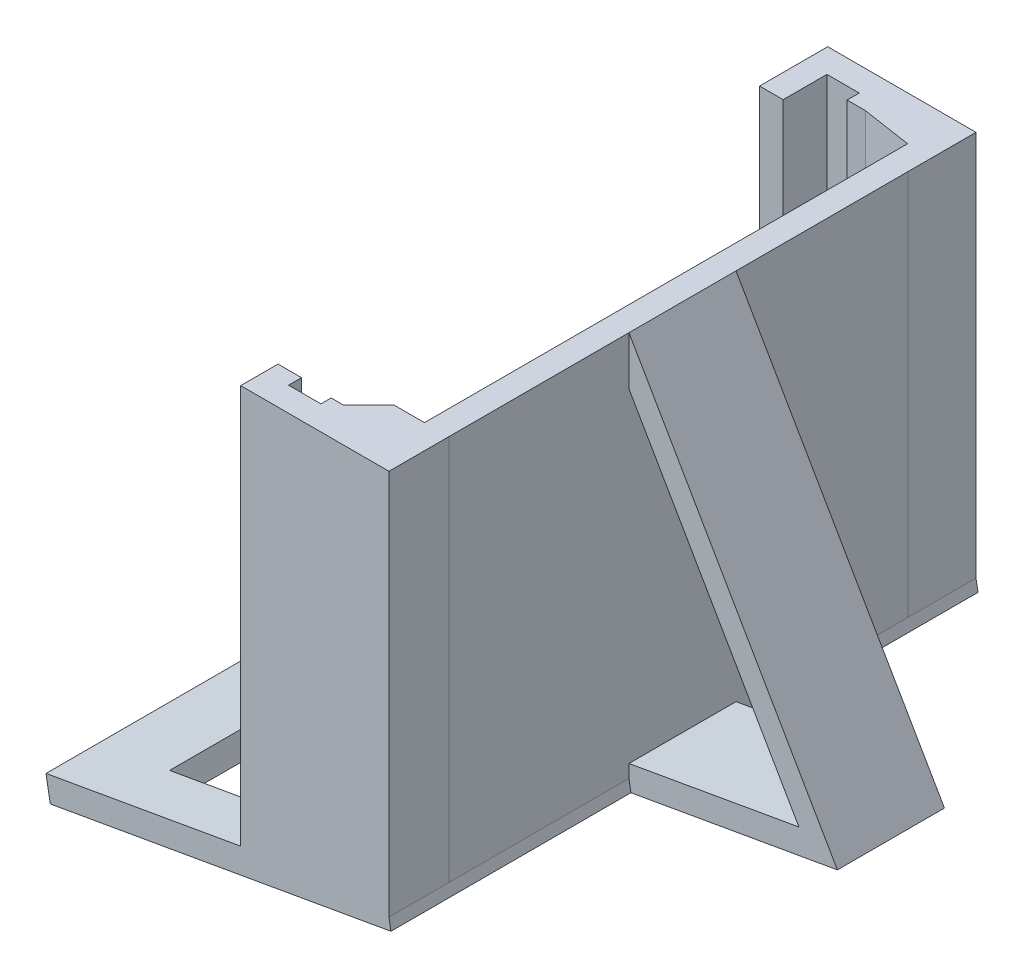
SolidWorks part; units mm, degrees
ref_plane "Front Plane" through (0, 0, 0) normal (0, 0, 1) x (1, 0, 0)
ref_plane "Top Plane" through (0, 0, 0) normal (0, 1, 0) x (1, 0, 0)
ref_plane "Right Plane" through (0, 0, 0) normal (1, 0, 0) x (0, 0, -1)
sketch "Sketch1" plane through (0, 0, 0) normal (0, 1, 0) x (1, 0, 0)
  line L1 (0, 0) -> (38.6999, 0)
  line L2 (0, 0) -> (0, 153.1937)
  line L3 (0, 153.1937) -> (38.6999, 153.1937)
  line L4 (38.6999, 0) -> (38.6999, 153.1937)
  dimension "D1" = 38.6999
  dimension "D2" = 153.1937
extrude "Boss-Extrude1" add sketch "Sketch1" along normal blind 0.0254 contours L1 L4 L3 L2 | L2 region at (19.35, 0, -76.5969)
sketch "Sketch3" plane through (0, 0.0254, 0) normal (0, 1, 0) x (1, 0, 0)
  line L0 (6.65, 146.8438) -> (6.15, 146.8438)
  line L1 (6.65, 146.8438) -> (14.5875, 146.8438)
  line L2 (14.5875, 146.8438) -> (14.5875, 143.6687)
  line L3 (14.5875, 143.6687) -> (32.05, 143.6687)
  line L4 (6.15, 146.8438) -> (6.15, 135.4137)
  line L7 (32.05, 143.6687) -> (32.35, 143.6687)
  line L8 (32.35, 143.6687) -> (32.35, 135.4137)
  line L9 (32.35, 135.4137) -> (38.7, 135.4137)
  line L10 (38.7, 135.4137) -> (38.7, 153.1937)
  line L11 (38.7, 153.1937) -> (0, 153.1937)
  line L12 (6.15, 135.4137) -> (0, 135.4137)
  line L13 (0, 153.1937) -> (0, 135.4137)
  line L15 (0, 153.1937) -> (38.6999, 153.1937) construction
  line L16 (14.5875, 9.025) -> (17.7625, 9.025)
  line L17 (10.6187, 146.8438) -> (10.6187, 76.5969) construction
  line L18 (10.6187, 76.5969) -> (61.4187, 76.5969) construction
  line L19 (38.6999, 0) -> (0, 0)
  line L20 (38.6999, 15.6157) -> (38.6999, 0)
  line L25 (14.5875, 6.35) -> (14.5875, 9.025)
  line L26 (6.65, 6.35) -> (14.5875, 6.35)
  line L27 (6.65, 6.35) -> (6.15, 6.35)
  line L28 (6.15, 6.35) -> (6.15, 9.7407)
  line L29 (6.15, 9.7407) -> (0, 9.7407)
  line L30 (0, 0) -> (0, 9.7407)
  line L31 (17.7625, 9.025) -> (24.3532, 15.6157)
  line L32 (24.3532, 15.6157) -> (38.6999, 15.6157)
  line L33 (19.35, 143.6687) -> (32.35, 141.6844)
  line L34 (38.6999, 0) -> (38.6999, 153.1937) construction
  line L35 (0, 0) -> (38.6999, 0) construction
  point P19 (10.6187, 146.8438)
  dimension "D1" = 17.4625
  dimension "D2" = 7.9375
  dimension "D3" = 3.175
  dimension "D4" = 11.43
  dimension "D5" = 0.5
  dimension "D6" = 0.3
  dimension "D7" = 0
  dimension "D8" = 38.6999
  dimension "D9" = 6.15
  dimension "D10" = 6.35
  dimension "D11" = 6.35
  dimension "D12" = 6.35
  dimension "D13" = 70.2469
  dimension "D14" = 50.8
  dimension "D15" = 3.175
  dimension "D16" = 135
  dimension "D17" = 14.3467
  dimension "D18" = 90
  dimension "D19" = 90
  dimension "D20" = 90
  dimension "D21" = 4.7625
  dimension "D22" = 1.9844
  dimension "D23" = 0
  dimension "D24" = 270
  dimension "D25" = 9.7407
  dimension "D26" = 6.5907
  dimension "D27" = 90
  dimension "D28" = 2.675
extrude "Boss-Extrude2" add sketch "Sketch3" along normal blind 104.14 contours L13 L12 L4 L0 L1 L2 L3 L7 L8 L9 L10 | L30 L19 L20 L25 L26 L27 L28 L29 | L3 L33 L8 L7 region at (19.9393, 0.0254, -146.561) region at (28.0167, 0.0254, -143.0073) region at (22.3528, 0.0254, -6.3762)
sketch "Sketch6" plane through (0, 0, -135.4137) normal (0, 0, 1) x (1, 0, 0)
  line L1 (32.35, 104.1654) -> (38.7, 104.1654)
  line L2 (32.35, 104.1654) -> (32.35, 0.0254)
  line L3 (32.35, 0.0254) -> (38.7, 0.0254)
  line L4 (38.7, 104.1654) -> (38.7, 0.0254)
  dimension "D1" = 104.14
  dimension "D2" = 6.35
extrude "Boss-Extrude3" add sketch "Sketch6" along normal up to surface (119.798 mm away) up to face at (31.5266, 52.0954, -15.6157)
sketch "Sketch15" plane through (0, 0, 0) normal (0, 0, 1) x (1, 0, 0)
  line L0 (0, 0) -> (38.6999, 0) construction
  line L1 (-50.8, -8.8719) -> (-49.6803, -15.2219)
  line L2 (127, 22.479) -> (-127, -22.3081) construction
  line L3 (0, 104.1654) -> (0, 0) construction
  line L4 (-49.6803, -15.2219) -> (39.2197, 0.4535)
  line L5 (39.2197, 0.4535) -> (38.1, 6.8035)
  line L6 (38.1, 6.8035) -> (-50.8, -8.8719)
  dimension "D1" = 10
  dimension "D2" = 254
  dimension "D3" = 127
  dimension "D4" = 22.479
  dimension "D5" = 6.35
  dimension "D6" = 88.9
  dimension "D7" = 38.1
extrude "Boss-Extrude7" add sketch "Sketch15" against normal up to surface (153.1937 mm away) up to face at (19.35, 52.0827, -153.1937)
sketch "Sketch11" plane through (0, 0, -153.1937) normal (0, 0, -1) x (-1, 0, 0)
  line L0 (-38.6999, 104.1654) -> (-93.0935, 9.9529)
  line L1 (-38.6999, 104.1654) -> (-38.6999, 3.4011) construction
  line L2 (-38.6999, 104.1654) -> (0, 104.1654) construction
  line L4 (-38.6999, 91.4654) -> (-86.4387, 8.7795)
  line L5 (-86.4387, 8.7795) -> (-93.0935, 9.9529)
  line L6 (-38.6999, 91.4654) -> (-38.6999, 104.1654)
  line L7 (49.6803, -15.2219) -> (-36.6476, 0) construction
  dimension "D1" = 12.7
  dimension "D2" = 30
  dimension "D3" = 0
  dimension "D4" = 30
  dimension "D5" = 12.7
  dimension "D6" = 0
extrude "Boss-Extrude5" add sketch "Sketch11" along direction (0, 0, -1) on the side against the normal blind 27.94 from offset 62.6269 contours L6 L0 L5 L4 offset against normal yes
sketch "Sketch14" plane through (0, 0, -153.1937) normal (0, 0, -1) x (-1, 0, 0)
  line L1 (-26, 40.005) -> (-14.5875, 40.005)
  line L2 (-26, 40.005) -> (-26, 59.055)
  line L3 (-26, 59.055) -> (-14.5875, 59.055)
  line L4 (-14.5875, 40.005) -> (-14.5875, 59.055)
  line L6 (-14.5875, 104.1654) -> (-14.5875, 2.6576) construction
  line L7 (-32.35, 104.1654) -> (-32.35, 5.7897) construction
  line L8 (0, 0.0855) -> (0, 104.1654) construction
  line L9 (0, 104.1654) -> (0, 0.0855) construction
  line L10 (0, 0.0855) -> (-39.2846, 0.0855) construction
  line L11 (-39.2197, 0.4535) -> (-38.6999, 3.4011) construction
  dimension "D1" = 19.05
  dimension "D2" = 39.9195
  dimension "D3" = 0
  dimension "D4" = 6.35
  dimension "D5" = 0
extrude "Cut-Extrude1" cut sketch "Sketch14" against normal up to next
sketch "Sketch18" plane through (38.1146, 6.7206, 0) normal (0.9848, 0.1736, 0) x (0, 0, -1)
  line L0 (153.1937, -6.3638) -> (0, -6.3638) construction
  line L1 (62.6269, -6.3638) -> (90.5669, -6.3638)
  line L2 (62.6269, -6.3638) -> (62.6269, -0.0138)
  line L3 (62.6269, -0.0138) -> (90.5669, -0.0138)
  line L4 (90.5669, -6.3638) -> (90.5669, -0.0138)
  line L5 (90.5669, 83.3556) -> (90.5669, -6.3638) construction
  dimension "D1" = 27.94
  dimension "D2" = 0
  dimension "D3" = 6.35
extrude "Boss-Extrude8" add sketch "Sketch18" along normal up to next
sketch "Sketch19" plane through (-0.0146, 0.0829, 0) normal (-0.1736, 0.9848, 0) x (0.9848, 0.1736, 0)
  line L0 (-51.5688, 153.1937) -> (-51.5688, 0) construction
  line L1 (-32.5188, 134.1437) -> (-13.4688, 134.1437)
  line L2 (-32.5188, 134.1437) -> (-32.5188, 115.0937)
  line L3 (-32.5188, 115.0937) -> (-13.4688, 115.0937)
  line L4 (-13.4688, 134.1437) -> (-13.4688, 115.0937)
  line L5 (0.0148, 153.1937) -> (-51.5688, 153.1937) construction
  line L6 (-32.5188, 108.7437) -> (-32.5188, 89.6937)
  line L7 (-32.5188, 108.7437) -> (-13.4688, 108.7437)
  line L8 (-13.4688, 108.7437) -> (-13.4688, 89.6937)
  line L9 (-32.5188, 89.6937) -> (-13.4688, 89.6937)
  line L10 (-32.5188, 83.3438) -> (-32.5188, 64.2938)
  line L11 (-32.5188, 83.3438) -> (-13.4688, 83.3438)
  line L12 (-13.4688, 83.3438) -> (-13.4688, 64.2938)
  line L13 (-32.5188, 64.2938) -> (-13.4688, 64.2938)
  line L14 (-32.5188, 57.9438) -> (-32.5188, 38.8938)
  line L15 (-32.5188, 57.9438) -> (-13.4688, 57.9438)
  line L16 (-13.4688, 57.9438) -> (-13.4688, 38.8938)
  line L17 (-32.5188, 38.8938) -> (-13.4688, 38.8938)
  line L18 (-32.5188, 32.5438) -> (-32.5188, 13.4938)
  line L19 (-32.5188, 32.5438) -> (-13.4688, 32.5438)
  line L20 (-13.4688, 32.5438) -> (-13.4688, 13.4938)
  line L21 (-32.5188, 13.4938) -> (-13.4688, 13.4938)
  dimension "D1" = 19.05
  dimension "D2" = 19.05
  dimension "D3" = 19.05
  dimension "D4" = 19.05
  dimension "D6" = 6.35
  dimension "D5" = 5
extrude "Cut-Extrude2" cut sketch "Sketch19" against normal through all
sketch "Sketch20" plane through (1.1051, -6.2671, 0) normal (0.1736, -0.9848, 0) x (0.9848, 0.1736, 0)
  line L1 (-47.8769, 185.4188) -> (88.0421, 185.4188)
  line L2 (-47.8769, 185.4188) -> (-47.8769, -314.6402)
  line L3 (-47.8769, -314.6402) -> (88.0421, -314.6402)
  line L4 (88.0421, 185.4188) -> (88.0421, -314.6402)
extrude "Cut-Extrude3" cut sketch "Sketch20" along normal blind 153.162
